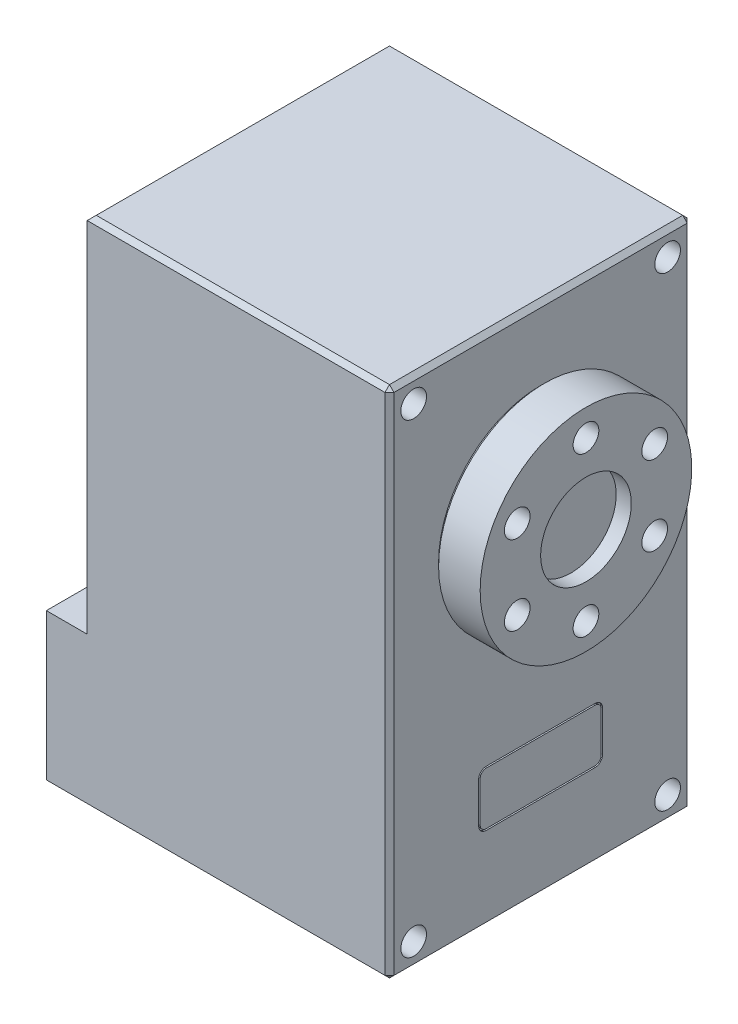
SolidWorks part; units mm, degrees
ref_plane "前视基准面" through (0, 0, 0) normal (0, 0, 1) x (1, 0, 0)
ref_plane "上视基准面" through (0, 0, 0) normal (0, 1, 0) x (1, 0, 0)
ref_plane "右视基准面" through (0, 0, 0) normal (1, 0, 0) x (0, 0, -1)
other "Configuration Table"
sketch "草图1" plane through (0, 0, 0) normal (0, 1, 0) x (1, 0, 0)
  line L1 (-10, -10) -> (10, -10)
  line L2 (-10, -10) -> (-10, 10)
  line L3 (-10, 10) -> (10, 10)
  line L4 (10, -10) -> (10, 10)
  line L5 (-10, -10) -> (10, 10) construction
  line L6 (-10, 10) -> (10, -10) construction
  point P0 (0, 0)
  dimension "D1" = 20
  dimension "D2" = 20
extrude "凸台-拉伸1" add sketch "草图1" along normal blind 34
sketch "草图2" plane through (-10, 0, 0) normal (-1, 0, 0) x (0, 0, 1)
  line L0 (0, 34) -> (0, 0) construction
  line L1 (-10, 34) -> (10, 34) construction
  circle A0 centre (0, 22.5) radius 6.75
  dimension "D2" = 13.5
  dimension "D1" = 11.5
extrude "凸台-拉伸3" add sketch "草图2" along normal blind 0.25
sketch "草图3" plane through (-10.25, 0, 0) normal (-1, 0, 0) x (0, 0, 1)
  circle A0 centre (0, 22.5) radius 7
  dimension "D1" = 14
extrude "凸台-拉伸4" add sketch "草图3" along normal blind 2.75
chamfer "倒角2" distance 0.25 angle 45 1 edges at (-10.25, 22.5, 6.75)
sketch "草图4" plane through (-13, 0, 0) normal (-1, 0, 0) x (0, 0, 1)
  circle A0 centre (0, 22.5) radius 5.25 construction
  circle A1 centre (0, 27.75) radius 0.85
  circle A2 centre (4.5466, 25.125) radius 0.85
  circle A3 centre (4.5466, 19.875) radius 0.85
  circle A4 centre (0, 17.25) radius 0.85
  circle A5 centre (-4.5466, 19.875) radius 0.85
  circle A6 centre (-4.5466, 25.125) radius 0.85
  point P17 (0, 22.5)
  dimension "D1" = 10.5
  dimension "D2" = 1.7
  dimension "D3" = 6
extrude "切除-拉伸1" cut sketch "草图4" against normal blind 3
mirror "镜向3" about plane through (0, 0, 0) normal (1, 0, 0) of "凸台-拉伸3", "凸台-拉伸4", "倒角2", "切除-拉伸1"
sketch "草图17" plane through (0, 0, 10) normal (0, 0, 1) x (1, 0, 0)
  line L1 (-10, 0) -> (-13, 0)
  line L2 (-10, 0) -> (-10, 10)
  line L3 (-10, 10) -> (-13, 10)
  line L4 (-13, 0) -> (-13, 10)
  dimension "D1" = 3
  dimension "D2" = 10
extrude "凸台-拉伸5" add sketch "草图17" against normal blind 20
sketch "草图22" plane through (0, 0, 0) normal (0, 0, 1) x (1, 0, 0)
  line L0 (-13, 10) -> (-10, 15.4143)
  line L2 (-10, 10) -> (-13, 10) construction
  line L3 (-10, 34) -> (-10, 10) construction
rib "筋16" sketch "草图22" sketch "草图22" thickness 8 extrusion direction parallel to sketch draft on no parameters "D1"=8
sketch "草图23" plane through (-13, 0, 0) normal (-1, 0, 0) x (0, 0, 1)
  line L0 (4, 15.4143) -> (4, 10) construction
  line L1 (-4, 15.4143) -> (4, 15.4143)
  arc A0 (-4, 15.4143) -> (4, 15.4143) centre (0, 19.4171) ccw
extrude "切除-拉伸4" cut sketch "草图23" against normal blind 3
sketch "草图24" plane through (-14.1857, 7.8601, 0) normal (-0.8747, 0.4847, 0) x (0, 0, 1)
  line L0 (0, 2.4465) -> (0, 8.6364) construction
  line L1 (-1.8527, 5.0706) -> (1.8527, 5.0706)
  line L2 (-1.8527, 5.0706) -> (-1.8527, 6.4792)
  line L3 (-1.8527, 6.4792) -> (1.8527, 6.4792)
  line L4 (1.8527, 5.0706) -> (1.8527, 6.4792)
  line L5 (-1.8527, 5.0706) -> (1.8527, 6.4792) construction
  line L6 (-1.8527, 6.4792) -> (1.8527, 5.0706) construction
  point P0 (0, 5.7749)
extrude "切除-拉伸-薄壁1" cut sketch "草图24" against normal blind 0.1 thin thin type one direction wall 0.1
sketch "草图25" plane through (10, 0, 0) normal (1, 0, 0) x (0, 0, -1)
  line L0 (0, 0) -> (0, 13.0314) construction
  line L2 (-3.5996, 5.6575) -> (3.5996, 5.6575)
  line L3 (-3.9996, 6.0575) -> (-3.9996, 8.73)
  line L4 (-3.5996, 9.13) -> (3.5996, 9.13)
  line L5 (3.9996, 6.0575) -> (3.9996, 8.73)
  line L6 (-3.9996, 5.6575) -> (3.9996, 9.13) construction
  line L7 (-3.9996, 9.13) -> (3.9996, 5.6575) construction
  arc A0 (-3.5996, 5.6575) -> (-3.9996, 6.0575) centre (-3.5996, 6.0575) cw
  arc A1 (3.5996, 5.6575) -> (3.9996, 6.0575) centre (3.5996, 6.0575) ccw
  arc A2 (3.5996, 9.13) -> (3.9996, 8.73) centre (3.5996, 8.73) cw
  arc A3 (-3.9996, 8.73) -> (-3.5996, 9.13) centre (-3.5996, 8.73) cw
  point P3 (0, 7.3938)
  dimension "D1" = 0.4
extrude "切除-拉伸-薄壁2" cut sketch "草图25" against normal blind 0.1 thin thin type one direction wall 0.1
sketch "草图26" plane through (-13, 0, 0) normal (-1, 0, 0) x (0, 0, 1)
  circle A0 centre (0, 22.5) radius 3
  dimension "D1" = 6
extrude "切除-拉伸5" cut sketch "草图26" against normal blind 1
mirror "镜向6" about plane through (0, 0, 0) normal (1, 0, 0) of "切除-拉伸5"
sketch "草图27" plane through (-13, 0, 0) normal (-1, 0, 0) x (0, 0, 1)
  line L0 (0, 0) -> (0, 6.6188) construction
  circle A0 centre (8.5194, 1.3852) radius 0.85
  circle A1 centre (-8.5194, 1.3852) radius 0.85
  dimension "D1" = 1.7
extrude "切除-拉伸6" cut sketch "草图27" against normal blind 3
sketch "草图28" plane through (-10, 0, 0) normal (-1, 0, 0) x (0, 0, 1)
  line L0 (8.5194, 1.3852) -> (8.5194, 36.2658) construction
  line L1 (0, 0) -> (0, 36.2658) construction
  line L2 (-10, 0) -> (10, 0) construction
  circle A0 centre (8.5194, 32.5825) radius 0.85
  circle A1 centre (-8.5194, 32.5825) radius 0.85
  dimension "D1" = 1.7
extrude "切除-拉伸7" cut sketch "草图28" against normal blind 3
sketch "草图30" plane through (10, 0, 0) normal (1, 0, 0) x (0, 0, -1)
  line L16 (-8.4, 1.6) -> (8.4, 1.6)
  line L17 (8.4, 1.6) -> (8.4, 32.4)
  line L18 (8.4, 32.4) -> (-8.4, 32.4)
  line L19 (-8.4, 32.4) -> (-8.4, 1.6)
  line L20 (-8.4, 1.6) -> (8.4, 1.6) construction
  line L21 (8.4, 1.6) -> (8.4, 32.4) construction
  line L22 (8.4, 32.4) -> (-8.4, 32.4) construction
  line L23 (-8.4, 32.4) -> (-8.4, 1.6) construction
  circle A0 centre (-8.4, 32.4) radius 0.85
  circle A1 centre (8.4, 32.4) radius 0.85
  circle A2 centre (8.4, 1.6) radius 0.85
  circle A3 centre (-8.4, 1.6) radius 0.85
  dimension "D2" = 1.7
  dimension "D3" = 1.7
  dimension "D4" = 1.7
  dimension "D5" = 1.7
  dimension "D1" = 1.6
extrude "切除-拉伸8" cut sketch "草图30" against normal blind 3
chamfer "倒角4" distance 0.3 angle 45 14 edges at (10, 17, -10) (0, 34, -10) (10, 34, 0) (-10, 34, 0) (0, 34, 10) (-13, 10, -7) (-13, 10, 7) (10, 17, 10) (10, 0, 0) (-1.5, 0, 10) (-13, 5, 10) (-13, 5, -10) (-1.5, 0, -10) (-13, 0, 0)
sketch "草图31" plane through (-10, 0, 0) normal (-1, 0, 0) x (0, 0, 1)
  line L0 (4, 10) -> (10, 10) construction
  line L1 (9.8, 10) -> (5.3, 10)
  line L2 (9.8, 10) -> (9.8, 17.5)
  line L3 (9.8, 17.5) -> (5.3, 17.5)
  line L4 (5.3, 10) -> (5.3, 17.5)
  line L5 (10, 33.7) -> (10, 10) construction
  dimension "D1" = 4.5
  dimension "D2" = 7.5
  dimension "D3" = 0.2
extrude "切除-拉伸9" cut sketch "草图31" against normal blind 6
sketch "草图32" plane through (-4, 0, 0) normal (-1, 0, 0) x (0, 0, 1)
  line L0 (5.3, 13.75) -> (11.6743, 13.75) construction
  line L1 (5.3, 17.5) -> (5.3, 10) construction
  line L2 (7, 13.75) -> (7, 16.6484) construction
  line L3 (6.75, 13.5) -> (7.25, 13.5)
  line L4 (6.75, 13.5) -> (6.75, 14)
  line L5 (6.75, 14) -> (7.25, 14)
  line L6 (7.25, 13.5) -> (7.25, 14)
  line L7 (6.75, 13.5) -> (7.25, 14) construction
  line L8 (6.75, 14) -> (7.25, 13.5) construction
  line L9 (6.75, 15.5) -> (7.25, 15.5)
  line L10 (6.75, 15.5) -> (6.75, 16)
  line L11 (6.75, 16) -> (7.25, 16)
  line L12 (7.25, 15.5) -> (7.25, 16)
  line L13 (6.75, 12) -> (6.75, 11.5)
  line L14 (6.75, 11.5) -> (7.25, 11.5)
  line L15 (7.25, 12) -> (7.25, 11.5)
  line L16 (6.75, 12) -> (7.25, 12)
  point P4 (7, 13.75)
  dimension "D1" = 0.5
  dimension "D2" = 0.5
  dimension "D3" = 1.7
  dimension "D4" = 1.5
  dimension "D5" = 0.5
  dimension "D6" = 0.5
extrude "凸台-拉伸6" add sketch "草图32" along normal blind 6
sketch "草图33" plane through (-4, 0, 0) normal (-1, 0, 0) x (0, 0, 1)
  line L0 (5.3, 10) -> (9.8, 10) construction
  line L1 (9.8, 17.5) -> (7.55, 17.5)
  line L2 (9.8, 17.5) -> (9.8, 10)
  line L3 (9.8, 10) -> (7.55, 10)
  line L4 (7.55, 17.5) -> (7.55, 10)
extrude "凸台-拉伸7" add sketch "草图33" along normal blind 0.3
chamfer "倒角5" distance 0.3 angle 45 1 edges at (-4, 13.75, 7.55)
sketch "草图34" plane through (-4.3, 0, 0) normal (-1, 0, 0) x (0, 0, 1)
  line L0 (7.25, 13.75) -> (12.7784, 13.75) construction
  line L1 (7.25, 13.5) -> (7.25, 14) construction
  line L2 (9.8, 10) -> (9.8, 17.5) construction
  line L3 (9.8, 14.55) -> (9.57, 14.55)
  line L4 (9.8, 14.55) -> (9.8, 15.05)
  line L5 (9.8, 15.05) -> (9.57, 15.05)
  line L6 (9.57, 14.55) -> (9.57, 15.05)
  line L7 (9.8, 12.45) -> (9.57, 12.45)
  line L8 (9.57, 12.95) -> (9.57, 12.45)
  line L9 (9.8, 12.95) -> (9.57, 12.95)
  line L10 (9.8, 12.95) -> (9.8, 12.45)
  dimension "D1" = 5.5284
  dimension "D2" = 0.8
  dimension "D3" = 0.23
  dimension "D4" = 0.5
extrude "凸台-拉伸8" add sketch "草图34" along normal blind 5.7
sketch "草图36" plane through (-10, 0, 0) normal (-1, 0, 0) x (0, 0, 1)
  line L0 (5.3, 13.75) -> (13.5972, 13.75) construction
  line L1 (5.3, 17.5) -> (5.3, 10) construction
  line L2 (5.3, 17.5) -> (5.3, 10) construction
  line L3 (5.3, 14.5553) -> (4.7976, 14.5553)
  line L4 (5.3, 14.5553) -> (5.3, 12.9447)
  line L5 (5.3, 12.9447) -> (4.7976, 12.9447)
  line L6 (4.7976, 14.5553) -> (4.7976, 12.9447)
extrude "切除-拉伸10" cut sketch "草图36" against normal blind 6
chamfer "倒角7" distance 0.2 angle 45 11 edges at (-10, 11.225, 9.8) (-10, 13.75, 9.8) (-10, 16.275, 9.8) (-10, 17.5, 7.55) (-10, 16.0277, 5.3) (-7, 12.9447, 5.3) (-10, 11.4723, 5.3) (-10, 12.9447, 5.0488) (-10, 13.75, 4.7976) (-10, 14.5553, 5.0488) (-7, 14.5553, 5.3)
mirror "镜向10" about plane through (0, 0, 0) normal (0, 0, 1) of "切除-拉伸10", "倒角5", "切除-拉伸9", "凸台-拉伸6", "凸台-拉伸7", "凸台-拉伸8"
chamfer "倒角8" distance 0.2 angle 45 9 edges at (-10, 11.225, -9.8) (-10, 13.75, -9.8) (-10, 11.4723, -5.3) (-10, 12.9447, -5.0488) (-10, 13.75, -4.7976) (-10, 14.5553, -5.0488) (-10, 16.0277, -5.3) (-10, 17.5, -7.55) (-10, 16.275, -9.8)
